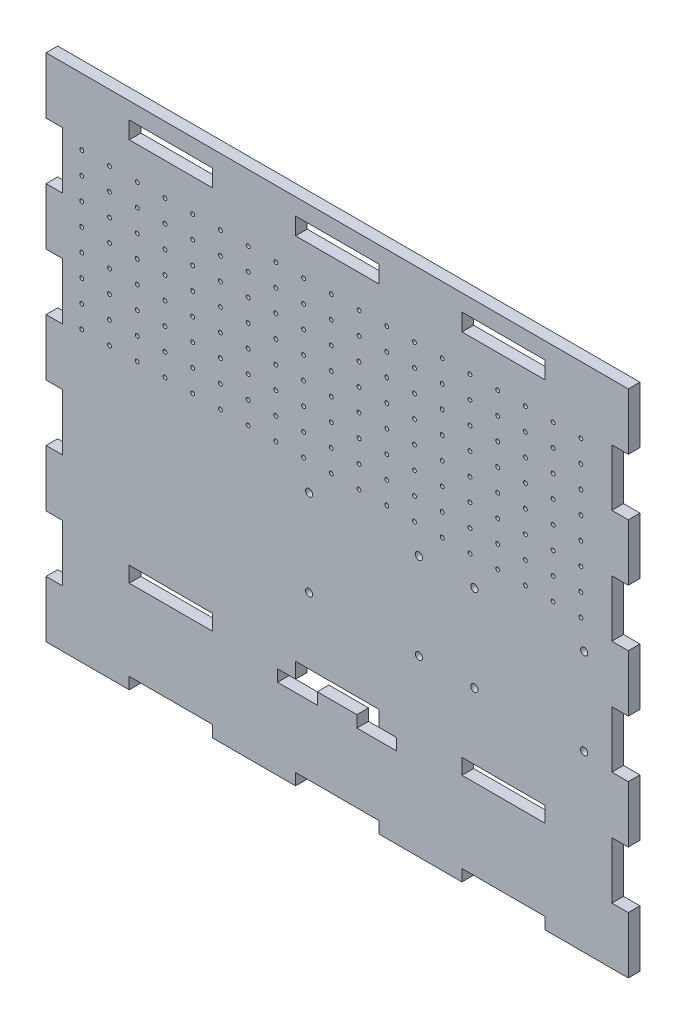
SolidWorks part; units mm, degrees
ref_plane "Front Plane" through (0, 0, 0) normal (0, 0, 1) x (1, 0, 0)
ref_plane "Top Plane" through (0, 0, 0) normal (0, 1, 0) x (1, 0, 0)
ref_plane "Right Plane" through (0, 0, 0) normal (1, 0, 0) x (0, 0, -1)
sketch "Sketch1" plane through (0, 0, 0) normal (0, 0, 1) x (1, 0, 0)
  line L1 (-127.8759, 139.2641) -> (138.8241, 139.2641)
  line L2 (-127.8759, 139.2641) -> (-127.8759, -84.2559)
  line L3 (-127.8759, -84.2559) -> (138.8241, -84.2559)
  line L4 (138.8241, 139.2641) -> (138.8241, -84.2559)
  dimension "D1" = 266.7
  dimension "D2" = 223.52
extrude "Boss-Extrude1" add sketch "Sketch1" along normal blind 5.334
sketch "Sketch2" plane through (0, 0, 5.334) normal (0, 0, 1) x (1, 0, 0)
  line L0 (-127.8759, -84.2559) -> (138.8241, -84.2559) construction
  line L1 (-89.7759, -84.2559) -> (-51.6759, -84.2559)
  line L2 (-89.7759, -84.2559) -> (-89.7759, -78.9219)
  line L3 (-89.7759, -78.9219) -> (-51.6759, -78.9219)
  line L4 (-51.6759, -84.2559) -> (-51.6759, -78.9219)
  line L5 (-89.7759, -78.9219) -> (-127.8759, -78.9219) construction
  line L6 (-13.5759, -84.2559) -> (24.5241, -84.2559)
  line L7 (-13.5759, -84.2559) -> (-13.5759, -78.9219)
  line L8 (-13.5759, -78.9219) -> (24.5241, -78.9219)
  line L9 (24.5241, -84.2559) -> (24.5241, -78.9219)
  line L10 (62.6241, -84.2559) -> (100.7241, -84.2559)
  line L11 (62.6241, -84.2559) -> (62.6241, -78.9219)
  line L12 (62.6241, -78.9219) -> (100.7241, -78.9219)
  line L13 (100.7241, -84.2559) -> (100.7241, -78.9219)
  line L14 (-127.8759, 139.2641) -> (-127.8759, -84.2559) construction
  line L15 (-51.6759, -78.9219) -> (-13.5759, -78.9219) construction
  line L16 (24.5241, -78.9219) -> (62.6241, -78.9219) construction
  line L17 (62.6241, -78.9219) -> (62.364, -79.7896) construction
  line L18 (100.7241, -78.9219) -> (138.8241, -78.9219) construction
  line L19 (138.8241, -84.2559) -> (138.8241, 139.2641) construction
  line L20 (-127.8759, 27.5041) -> (138.8241, 27.5041) construction
  line L21 (100.7241, 139.2641) -> (100.7241, 133.9301)
  line L22 (62.6241, 133.9301) -> (100.7241, 133.9301)
  line L23 (62.6241, 139.2641) -> (62.6241, 133.9301)
  line L24 (24.5241, 139.2641) -> (24.5241, 133.9301)
  line L25 (-13.5759, 133.9301) -> (24.5241, 133.9301)
  line L26 (-13.5759, 139.2641) -> (-13.5759, 133.9301)
  line L27 (-51.6759, 139.2641) -> (-51.6759, 133.9301)
  line L28 (-89.7759, 133.9301) -> (-51.6759, 133.9301)
  line L29 (-89.7759, 139.2641) -> (-89.7759, 133.9301)
  line L30 (62.6241, 139.2641) -> (100.7241, 139.2641)
  line L31 (-13.5759, 139.2641) -> (24.5241, 139.2641)
  line L32 (-89.7759, 139.2641) -> (-51.6759, 139.2641)
  dimension "D1" = 5.334
extrude "Cut-Extrude1" cut sketch "Sketch2" against normal through all
sketch "Sketch5" plane through (0, 0, 5.334) normal (0, 0, 1) x (1, 0, 0)
  line L0 (-51.6759, -34.8224) -> (-13.5759, -34.8224) construction
  line L1 (-89.7759, -34.8224) -> (-51.6759, -34.8224)
  line L2 (-89.7759, -34.8224) -> (-89.7759, -41.9344)
  line L3 (-89.7759, -41.9344) -> (-51.6759, -41.9344)
  line L4 (-51.6759, -34.8224) -> (-51.6759, -41.9344)
  line L5 (-13.5759, -34.8224) -> (24.5241, -34.8224)
  line L6 (-13.5759, -34.8224) -> (-13.5759, -41.9344)
  line L7 (-13.5759, -41.9344) -> (24.5241, -41.9344)
  line L8 (24.5241, -34.8224) -> (24.5241, -41.9344)
  line L9 (62.6241, -34.8224) -> (100.7241, -34.8224)
  line L10 (62.6241, -34.8224) -> (62.6241, -41.9344)
  line L11 (62.6241, -41.9344) -> (100.7241, -41.9344)
  line L12 (100.7241, -34.8224) -> (100.7241, -41.9344)
  line L13 (-51.6759, -41.9344) -> (-13.5759, -41.9344) construction
  line L14 (24.5241, -34.8224) -> (62.6241, -34.8224) construction
  line L15 (24.5241, -41.9344) -> (62.6241, -41.9344) construction
  line L16 (-89.7759, -34.8224) -> (-127.8759, -34.8224) construction
  line L17 (-127.8759, 139.2641) -> (-127.8759, -84.2559) construction
  line L18 (-89.7759, -41.9344) -> (-127.8759, -41.9344) construction
  line L19 (100.7241, -34.8224) -> (138.8241, -34.8224) construction
  line L20 (138.8241, -84.2559) -> (138.8241, 139.2641) construction
  line L21 (100.7241, -41.9344) -> (138.8241, -41.9344) construction
  dimension "D1" = 7.112
extrude "Cut-Extrude3" cut sketch "Sketch5" against normal through all
sketch "Sketch8" plane through (0, 0, 5.334) normal (0, 0, 1) x (1, 0, 0)
  line L0 (-13.5759, -41.9344) -> (24.5241, -41.9344) construction
  line L1 (-21.7977, -47.2684) -> (-3.6478, -47.2684)
  line L2 (-21.7977, -47.2684) -> (-21.7977, -41.9344)
  line L3 (-21.7977, -41.9344) -> (-3.6478, -41.9344)
  line L4 (-3.6478, -47.2684) -> (-3.6478, -41.9344)
  line L5 (-3.6478, -47.2684) -> (14.5022, -47.2684) construction
  line L6 (14.5022, -41.9344) -> (32.6521, -41.9344)
  line L7 (14.5022, -41.9344) -> (14.5022, -47.2684)
  line L8 (14.5022, -47.2684) -> (32.6521, -47.2684)
  line L9 (32.6521, -41.9344) -> (32.6521, -47.2684)
  line L10 (14.5022, -47.2684) -> (14.3218, -49.4005) construction
  line L11 (14.5022, -41.9344) -> (-3.6478, -41.9344) construction
  line L12 (62.6241, -34.8224) -> (62.6241, -41.9344) construction
  line L13 (-51.6759, -41.9344) -> (-51.6759, -34.8224) construction
  dimension "D1" = 5.334
  dimension "D2" = 29.972
  dimension "D3" = 29.8782
extrude "Cut-Extrude6" cut sketch "Sketch8" against normal through all
sketch "Sketch9" plane through (0, 0, 5.334) normal (0, 0, 1) x (1, 0, 0)
  line L0 (-111.5143, 118.9789) -> (-98.8143, 118.9789) construction
  line L1 (-111.5143, 108.8189) -> (-98.8143, 108.8189) construction
  line L2 (-111.5143, 98.6589) -> (-98.8143, 98.6589) construction
  line L3 (-111.5143, 88.4989) -> (-98.8143, 88.4989) construction
  line L4 (-111.5143, 78.3389) -> (-98.8143, 78.3389) construction
  line L5 (-111.5143, 68.1789) -> (-98.8143, 68.1789) construction
  line L6 (-111.5143, 58.0189) -> (-98.8143, 58.0189) construction
  line L7 (-111.5143, 47.8589) -> (-98.8143, 47.8589) construction
  line L8 (-111.5143, 118.9789) -> (-111.5143, 108.8189) construction
  circle A0 centre (-111.5143, 118.9789) radius 0.889
  circle A1 centre (-98.8143, 118.9789) radius 0.889
  circle A2 centre (-86.1143, 118.9789) radius 0.889
  circle A3 centre (-73.4143, 118.9789) radius 0.889
  circle A4 centre (-60.7143, 118.9789) radius 0.889
  circle A5 centre (-48.0143, 118.9789) radius 0.889
  circle A6 centre (-35.3143, 118.9789) radius 0.889
  circle A7 centre (-22.6143, 118.9789) radius 0.889
  circle A8 centre (-9.9143, 118.9789) radius 0.889
  circle A9 centre (2.7857, 118.9789) radius 0.889
  circle A10 centre (15.4857, 118.9789) radius 0.889
  circle A11 centre (28.1857, 118.9789) radius 0.889
  circle A12 centre (40.8857, 118.9789) radius 0.889
  circle A13 centre (53.5857, 118.9789) radius 0.889
  circle A14 centre (66.2857, 118.9789) radius 0.889
  circle A15 centre (78.9857, 118.9789) radius 0.889
  circle A16 centre (91.6857, 118.9789) radius 0.889
  circle A17 centre (104.3857, 118.9789) radius 0.889
  circle A18 centre (117.0857, 118.9789) radius 0.889
  circle A19 centre (-111.5143, 108.8189) radius 0.889
  circle A20 centre (-98.8143, 108.8189) radius 0.889
  circle A21 centre (-86.1143, 108.8189) radius 0.889
  circle A22 centre (-73.4143, 108.8189) radius 0.889
  circle A23 centre (-60.7143, 108.8189) radius 0.889
  circle A24 centre (-48.0143, 108.8189) radius 0.889
  circle A25 centre (-35.3143, 108.8189) radius 0.889
  circle A26 centre (-22.6143, 108.8189) radius 0.889
  circle A27 centre (-9.9143, 108.8189) radius 0.889
  circle A28 centre (2.7857, 108.8189) radius 0.889
  circle A29 centre (15.4857, 108.8189) radius 0.889
  circle A30 centre (28.1857, 108.8189) radius 0.889
  circle A31 centre (40.8857, 108.8189) radius 0.889
  circle A32 centre (53.5857, 108.8189) radius 0.889
  circle A33 centre (66.2857, 108.8189) radius 0.889
  circle A34 centre (78.9857, 108.8189) radius 0.889
  circle A35 centre (91.6857, 108.8189) radius 0.889
  circle A36 centre (104.3857, 108.8189) radius 0.889
  circle A37 centre (117.0857, 108.8189) radius 0.889
  circle A38 centre (-111.5143, 98.6589) radius 0.889
  circle A39 centre (-98.8143, 98.6589) radius 0.889
  circle A40 centre (-86.1143, 98.6589) radius 0.889
  circle A41 centre (-73.4143, 98.6589) radius 0.889
  circle A42 centre (-60.7143, 98.6589) radius 0.889
  circle A43 centre (-48.0143, 98.6589) radius 0.889
  circle A44 centre (-35.3143, 98.6589) radius 0.889
  circle A45 centre (-22.6143, 98.6589) radius 0.889
  circle A46 centre (-9.9143, 98.6589) radius 0.889
  circle A47 centre (2.7857, 98.6589) radius 0.889
  circle A48 centre (15.4857, 98.6589) radius 0.889
  circle A49 centre (28.1857, 98.6589) radius 0.889
  circle A50 centre (40.8857, 98.6589) radius 0.889
  circle A51 centre (53.5857, 98.6589) radius 0.889
  circle A52 centre (66.2857, 98.6589) radius 0.889
  circle A53 centre (78.9857, 98.6589) radius 0.889
  circle A54 centre (91.6857, 98.6589) radius 0.889
  circle A55 centre (104.3857, 98.6589) radius 0.889
  circle A56 centre (117.0857, 98.6589) radius 0.889
  circle A57 centre (-111.5143, 88.4989) radius 0.889
  circle A58 centre (-98.8143, 88.4989) radius 0.889
  circle A59 centre (-86.1143, 88.4989) radius 0.889
  circle A60 centre (-73.4143, 88.4989) radius 0.889
  circle A61 centre (-60.7143, 88.4989) radius 0.889
  circle A62 centre (-48.0143, 88.4989) radius 0.889
  circle A63 centre (-35.3143, 88.4989) radius 0.889
  circle A64 centre (-22.6143, 88.4989) radius 0.889
  circle A65 centre (-9.9143, 88.4989) radius 0.889
  circle A66 centre (2.7857, 88.4989) radius 0.889
  circle A67 centre (15.4857, 88.4989) radius 0.889
  circle A68 centre (28.1857, 88.4989) radius 0.889
  circle A69 centre (40.8857, 88.4989) radius 0.889
  circle A70 centre (53.5857, 88.4989) radius 0.889
  circle A71 centre (66.2857, 88.4989) radius 0.889
  circle A72 centre (78.9857, 88.4989) radius 0.889
  circle A73 centre (91.6857, 88.4989) radius 0.889
  circle A74 centre (104.3857, 88.4989) radius 0.889
  circle A75 centre (117.0857, 88.4989) radius 0.889
  circle A76 centre (-111.5143, 78.3389) radius 0.889
  circle A77 centre (-98.8143, 78.3389) radius 0.889
  circle A78 centre (-86.1143, 78.3389) radius 0.889
  circle A79 centre (-73.4143, 78.3389) radius 0.889
  circle A80 centre (-60.7143, 78.3389) radius 0.889
  circle A81 centre (-48.0143, 78.3389) radius 0.889
  circle A82 centre (-35.3143, 78.3389) radius 0.889
  circle A83 centre (-22.6143, 78.3389) radius 0.889
  circle A84 centre (-9.9143, 78.3389) radius 0.889
  circle A85 centre (2.7857, 78.3389) radius 0.889
  circle A86 centre (15.4857, 78.3389) radius 0.889
  circle A87 centre (28.1857, 78.3389) radius 0.889
  circle A88 centre (40.8857, 78.3389) radius 0.889
  circle A89 centre (53.5857, 78.3389) radius 0.889
  circle A90 centre (66.2857, 78.3389) radius 0.889
  circle A91 centre (78.9857, 78.3389) radius 0.889
  circle A92 centre (91.6857, 78.3389) radius 0.889
  circle A93 centre (104.3857, 78.3389) radius 0.889
  circle A94 centre (117.0857, 78.3389) radius 0.889
  circle A95 centre (-111.5143, 68.1789) radius 0.889
  circle A96 centre (-98.8143, 68.1789) radius 0.889
  circle A97 centre (-86.1143, 68.1789) radius 0.889
  circle A98 centre (-73.4143, 68.1789) radius 0.889
  circle A99 centre (-60.7143, 68.1789) radius 0.889
  circle A100 centre (-48.0143, 68.1789) radius 0.889
  circle A101 centre (-35.3143, 68.1789) radius 0.889
  circle A102 centre (-22.6143, 68.1789) radius 0.889
  circle A103 centre (-9.9143, 68.1789) radius 0.889
  circle A104 centre (2.7857, 68.1789) radius 0.889
  circle A105 centre (15.4857, 68.1789) radius 0.889
  circle A106 centre (28.1857, 68.1789) radius 0.889
  circle A107 centre (40.8857, 68.1789) radius 0.889
  circle A108 centre (53.5857, 68.1789) radius 0.889
  circle A109 centre (66.2857, 68.1789) radius 0.889
  circle A110 centre (78.9857, 68.1789) radius 0.889
  circle A111 centre (91.6857, 68.1789) radius 0.889
  circle A112 centre (104.3857, 68.1789) radius 0.889
  circle A113 centre (117.0857, 68.1789) radius 0.889
  circle A114 centre (-111.5143, 58.0189) radius 0.889
  circle A115 centre (-98.8143, 58.0189) radius 0.889
  circle A116 centre (-86.1143, 58.0189) radius 0.889
  circle A117 centre (-73.4143, 58.0189) radius 0.889
  circle A118 centre (-60.7143, 58.0189) radius 0.889
  circle A119 centre (-48.0143, 58.0189) radius 0.889
  circle A120 centre (-35.3143, 58.0189) radius 0.889
  circle A121 centre (-22.6143, 58.0189) radius 0.889
  circle A122 centre (-9.9143, 58.0189) radius 0.889
  circle A123 centre (2.7857, 58.0189) radius 0.889
  circle A124 centre (15.4857, 58.0189) radius 0.889
  circle A125 centre (28.1857, 58.0189) radius 0.889
  circle A126 centre (40.8857, 58.0189) radius 0.889
  circle A127 centre (53.5857, 58.0189) radius 0.889
  circle A128 centre (66.2857, 58.0189) radius 0.889
  circle A129 centre (78.9857, 58.0189) radius 0.889
  circle A130 centre (91.6857, 58.0189) radius 0.889
  circle A131 centre (104.3857, 58.0189) radius 0.889
  circle A132 centre (117.0857, 58.0189) radius 0.889
  circle A133 centre (-111.5143, 47.8589) radius 0.889
  circle A134 centre (-98.8143, 47.8589) radius 0.889
  circle A135 centre (-86.1143, 47.8589) radius 0.889
  circle A136 centre (-73.4143, 47.8589) radius 0.889
  circle A137 centre (-60.7143, 47.8589) radius 0.889
  circle A138 centre (-48.0143, 47.8589) radius 0.889
  circle A139 centre (-35.3143, 47.8589) radius 0.889
  circle A140 centre (-22.6143, 47.8589) radius 0.889
  circle A141 centre (-9.9143, 47.8589) radius 0.889
  circle A142 centre (2.7857, 47.8589) radius 0.889
  circle A143 centre (15.4857, 47.8589) radius 0.889
  circle A144 centre (28.1857, 47.8589) radius 0.889
  circle A145 centre (40.8857, 47.8589) radius 0.889
  circle A146 centre (53.5857, 47.8589) radius 0.889
  circle A147 centre (66.2857, 47.8589) radius 0.889
  circle A148 centre (78.9857, 47.8589) radius 0.889
  circle A149 centre (91.6857, 47.8589) radius 0.889
  circle A150 centre (104.3857, 47.8589) radius 0.889
  circle A151 centre (117.0857, 47.8589) radius 0.889
  dimension "D1" = 19
  dimension "D5" = 1.778
  dimension "D2" = 12.7
  dimension "D4" = 10.16
  dimension "D3" = 8
extrude "Cut-Extrude7" cut sketch "Sketch9" against normal through all
sketch "Sketch10" plane through (0, 139.2641, 0) normal (0, 1, 0) x (1, 0, 0)
  line L0 (-13.5759, -5.334) -> (-51.6759, -5.334) construction
  line L1 (-51.6759, 0) -> (-13.5759, 0)
  line L2 (-51.6759, 0) -> (-51.6759, -5.334)
  line L3 (-51.6759, -5.334) -> (-13.5759, -5.334)
  line L4 (-13.5759, 0) -> (-13.5759, -5.334)
extrude "Boss-Extrude2" add sketch "Sketch10" along normal blind 10.16
sketch "Sketch12" plane through (-51.6759, 0, 0) normal (-1, 0, 0) x (0, 0, 1)
  line L0 (0, 133.9301) -> (0, 149.4241) construction
  line L1 (5.334, 149.4241) -> (0, 149.4241)
  line L2 (5.334, 149.4241) -> (5.334, 141.8041)
  line L3 (5.334, 141.8041) -> (0, 141.8041)
  line L4 (0, 149.4241) -> (0, 141.8041)
  dimension "D1" = 7.62
extrude "Boss-Extrude3" add sketch "Sketch12" along normal blind 76.2 and the other way blind 190.5
sketch "Sketch13" plane through (0, 139.2641, 0) normal (0, 1, 0) x (1, 0, 0)
  line L1 (-127.8759, 0) -> (-89.7759, 0)
  line L2 (-127.8759, 0) -> (-127.8759, -5.334)
  line L3 (-127.8759, -5.334) -> (-89.7759, -5.334)
  line L4 (-89.7759, 0) -> (-89.7759, -5.334)
extrude "Boss-Extrude4" add sketch "Sketch13" along normal blind 2.54
sketch "Sketch14" plane through (0, 139.2641, 0) normal (0, 1, 0) x (1, 0, 0)
  line L1 (24.5241, 0) -> (62.6241, 0)
  line L2 (24.5241, 0) -> (24.5241, -5.334)
  line L3 (24.5241, -5.334) -> (62.6241, -5.334)
  line L4 (62.6241, 0) -> (62.6241, -5.334)
extrude "Boss-Extrude5" add sketch "Sketch14" along normal blind 2.54
sketch "Sketch15" plane through (0, 139.2641, 0) normal (0, 1, 0) x (1, 0, 0)
  line L1 (100.7241, 0) -> (138.8241, 0)
  line L2 (100.7241, 0) -> (100.7241, -5.334)
  line L3 (100.7241, -5.334) -> (138.8241, -5.334)
  line L4 (138.8241, 0) -> (138.8241, -5.334)
extrude "Boss-Extrude6" add sketch "Sketch15" along normal blind 2.54
sketch "Sketch16" plane through (0, 0, 5.334) normal (0, 0, 1) x (1, 0, 0)
  line L0 (-127.8759, 149.4241) -> (-127.8759, -84.2559) construction
  line L1 (-127.8759, -32.327) -> (-120.3498, -32.327)
  line L2 (-127.8759, -32.327) -> (-127.8759, -58.2914)
  line L3 (-127.8759, -58.2914) -> (-120.3498, -58.2914)
  line L4 (-120.3498, -32.327) -> (-120.3498, -58.2914)
  line L5 (-120.3498, -32.327) -> (-120.3498, -6.3625) construction
  line L6 (-127.8759, 19.6019) -> (-120.3498, 19.6019)
  line L7 (-120.3498, -58.2914) -> (-120.3498, -84.2559) construction
  line L8 (-127.8759, -84.2559) -> (-89.7759, -84.2559) construction
  line L9 (-127.8759, 19.6019) -> (-127.8759, -6.3625)
  line L10 (-127.8759, -6.3625) -> (-120.3498, -6.3625)
  line L11 (-120.3498, 19.6019) -> (-120.3498, -6.3625)
  line L12 (-120.3498, 19.6019) -> (-120.3498, 45.5664) construction
  line L13 (5.4741, -78.9219) -> (5.4741, 149.4241) construction
  line L14 (-127.8759, 71.5308) -> (-120.3498, 71.5308)
  line L15 (-127.8759, 71.5308) -> (-127.8759, 45.5664)
  line L16 (-127.8759, 45.5664) -> (-120.3498, 45.5664)
  line L17 (-120.3498, 71.5308) -> (-120.3498, 45.5664)
  line L18 (-120.3498, 71.5308) -> (-120.3498, 97.4953) construction
  line L19 (24.5241, -78.9219) -> (-13.5759, -78.9219) construction
  line L20 (-127.8759, 97.4953) -> (-120.3498, 97.4953)
  line L21 (-127.8759, 97.4953) -> (-127.8759, 123.4597)
  line L22 (-127.8759, 123.4597) -> (-120.3498, 123.4597)
  line L23 (-120.3498, 97.4953) -> (-120.3498, 123.4597)
  line L24 (-120.3498, 123.4597) -> (-120.3498, 149.4241) construction
  line L25 (-127.8759, 149.4241) -> (138.8241, 149.4241) construction
  line L26 (131.298, 123.4597) -> (131.298, 149.4241) construction
  line L27 (131.298, 71.5308) -> (131.298, 97.4953) construction
  line L28 (131.298, 19.6019) -> (131.298, 45.5664) construction
  line L29 (131.298, -58.2914) -> (131.298, -84.2559) construction
  line L30 (131.298, -32.327) -> (131.298, -6.3625) construction
  line L31 (131.298, 97.4953) -> (131.298, 123.4597)
  line L32 (138.8241, 123.4597) -> (131.298, 123.4597)
  line L33 (138.8241, 97.4953) -> (138.8241, 123.4597)
  line L34 (138.8241, 97.4953) -> (131.298, 97.4953)
  line L35 (131.298, 71.5308) -> (131.298, 45.5664)
  line L36 (138.8241, 45.5664) -> (131.298, 45.5664)
  line L37 (138.8241, 71.5308) -> (138.8241, 45.5664)
  line L38 (138.8241, 71.5308) -> (131.298, 71.5308)
  line L39 (131.298, 19.6019) -> (131.298, -6.3625)
  line L40 (138.8241, -6.3625) -> (131.298, -6.3625)
  line L41 (138.8241, 19.6019) -> (138.8241, -6.3625)
  line L42 (138.8241, 19.6019) -> (131.298, 19.6019)
  line L43 (131.298, -32.327) -> (131.298, -58.2914)
  line L44 (138.8241, -58.2914) -> (131.298, -58.2914)
  line L45 (138.8241, -32.327) -> (138.8241, -58.2914)
  line L46 (138.8241, -32.327) -> (131.298, -32.327)
extrude "Cut-Extrude9" cut sketch "Sketch16" against normal through all
sketch "Sketch17" plane through (0, 0, 5.334) normal (0, 0, 1) x (1, 0, 0)
  line L1 (131.298, 71.5308) -> (131.298, 45.5664) construction
  circle A0 centre (118.598, 35.1589) radius 1.651
  circle A1 centre (117.0857, 47.8589) radius 0.889 construction
  circle A2 centre (68.306, 35.1589) radius 1.651
  circle A3 centre (68.306, -4.4651) radius 1.651
  circle A4 centre (118.598, -4.4651) radius 1.651
  circle A5 centre (42.906, 35.1589) radius 1.651
  circle A6 centre (-7.386, 35.1589) radius 1.651
  circle A7 centre (-7.386, -4.4651) radius 1.651
  circle A8 centre (42.906, -4.4651) radius 1.651
  dimension "D1" = 12.7
  dimension "D2" = 12.7
  dimension "D3" = 2
  dimension "D4" = 2
  dimension "D5" = 2
  dimension "D6" = 2
  dimension "D7" = 2
extrude "Cut-Extrude10" cut sketch "Sketch17" against normal through all
equation "\"MDF\"= .21in"
equation "\"Foamcore\"= .13in"
equation "\"Gmaterial\"= \"MDF\""
equation "\"D1@Boss-Extrude1\"=\"MDF\""
equation "\"D1@Sketch2\"=\"MDF\""
equation "\"D1@Sketch5\"=\"MDF\"+0.07"
equation "\"D1@Sketch8\"=\"MDF\""
